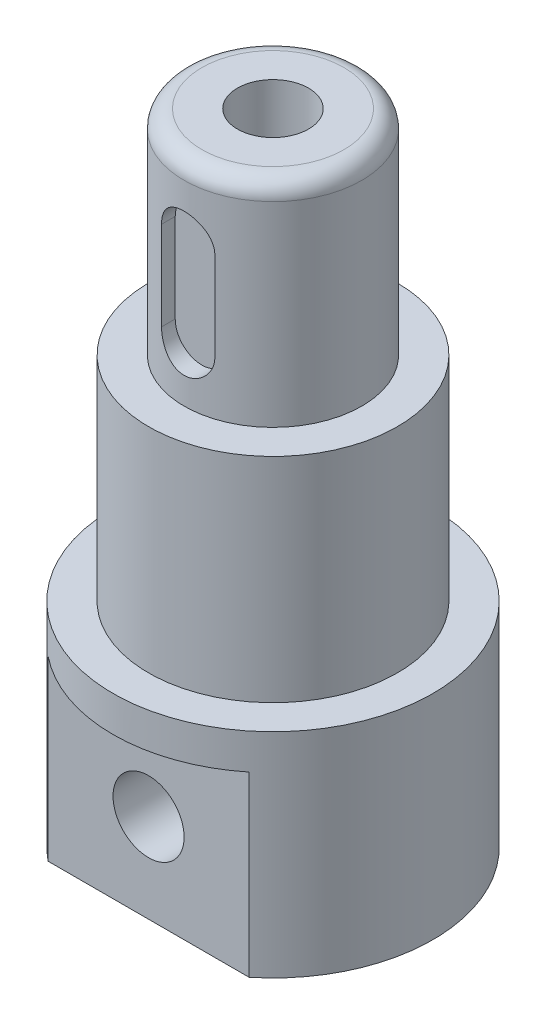
SolidWorks part; units mm, degrees
material "1023 Carbon Steel Sheet (SS)"
ref_plane "Front Plane" through (0, 0, 0) normal (0, 0, 1) x (1, 0, 0)
ref_plane "Top Plane" through (0, 0, 0) normal (0, 1, 0) x (1, 0, 0)
ref_plane "Right Plane" through (0, 0, 0) normal (1, 0, 0) x (0, 0, -1)
sketch "Sketch1" plane through (0, 0, 0) normal (0, 0, 1) x (1, 0, 0)
  line L0 (0, -36) -> (0, 36) construction
  line L1 (18, -36) -> (18, -12)
  line L2 (18, -12) -> (14, -12)
  line L3 (14, -12) -> (14, 12)
  line L4 (14, 12) -> (10, 12)
  line L5 (10, 12) -> (10, 34)
  line L6 (8, 36) -> (4, 36)
  line L7 (4, 36) -> (4, -36)
  line L8 (4, -36) -> (18, -36)
  arc A0 (10, 34) -> (8, 36) centre (8, 34) ccw
  point P11 (16, -12)
  point P12 (6, 36)
  dimension "D9" = 2
  dimension "D1" = 72
  dimension "D2" = 4
  dimension "D3" = 24
  dimension "D4" = 24
  dimension "D5" = 24
  dimension "D6" = 10
  dimension "D7" = 4
  dimension "D8" = 4
revolve "Revolve1" add sketch "Sketch1" angle 360 about L0
sketch "Sketch2" plane through (0, 0, 0) normal (0, 0, 1) x (1, 0, 0)
  line L0 (18, -12) -> (-18, -12) construction
  line L1 (-15, -16) -> (15, -16)
  line L2 (-15, -16) -> (-15, -41.4604)
  line L3 (-15, -41.4604) -> (15, -41.4604)
  line L4 (15, -16) -> (15, -41.4604)
  circle A0 centre (0, -26) radius 4
  point P4 (0, -16)
  dimension "D3" = 8
  dimension "D1" = 30
  dimension "D2" = 4
  dimension "D4" = 10
extrude "Cut-Extrude2" cut sketch "Sketch2" against normal through all both and the other way through all contours A0
extrude "Cut-Extrude3" cut sketch "Sketch2<4>" against normal through all from offset 14 offset against normal yes
sketch "Sketch2<4>" plane through (0, 0, 0) normal (0, 0, 1) x (1, 0, 0) same geometry as "Sketch2"
extrude "Cut-Extrude4" cut sketch "Sketch2<5>" along normal through all from offset 14
sketch "Sketch2<5>" plane through (0, 0, 0) normal (0, 0, 1) x (1, 0, 0) same geometry as "Sketch2"
sketch "Sketch4" plane through (0, 0, 0) normal (0, 0, 1) x (1, 0, 0)
  line L0 (0, 28) -> (0, 18) construction
  line L1 (3, 28) -> (3, 18)
  line L2 (-3, 28) -> (-3, 18)
  line L3 (10, 23) -> (-10, 23) construction
  line L4 (10, 12) -> (10, 34) construction
  line L5 (-10, 34) -> (-10, 12) construction
  arc A0 (3, 28) -> (-3, 28) centre (0, 28) ccw
  arc A1 (-3, 18) -> (3, 18) centre (0, 18) ccw
  point P2 (0, 23)
  point P14 (0, 0)
  dimension "D1" = 3
  dimension "D2" = 10
extrude "Cut-Extrude5" cut sketch "Sketch4" against normal blind 10 from offset 8 offset against normal yes
extrude "Cut-Extrude6" cut sketch "Sketch4<2>" along normal blind 10 from offset 8
sketch "Sketch4<2>" plane through (0, 0, 0) normal (0, 0, 1) x (1, 0, 0) same geometry as "Sketch4"
